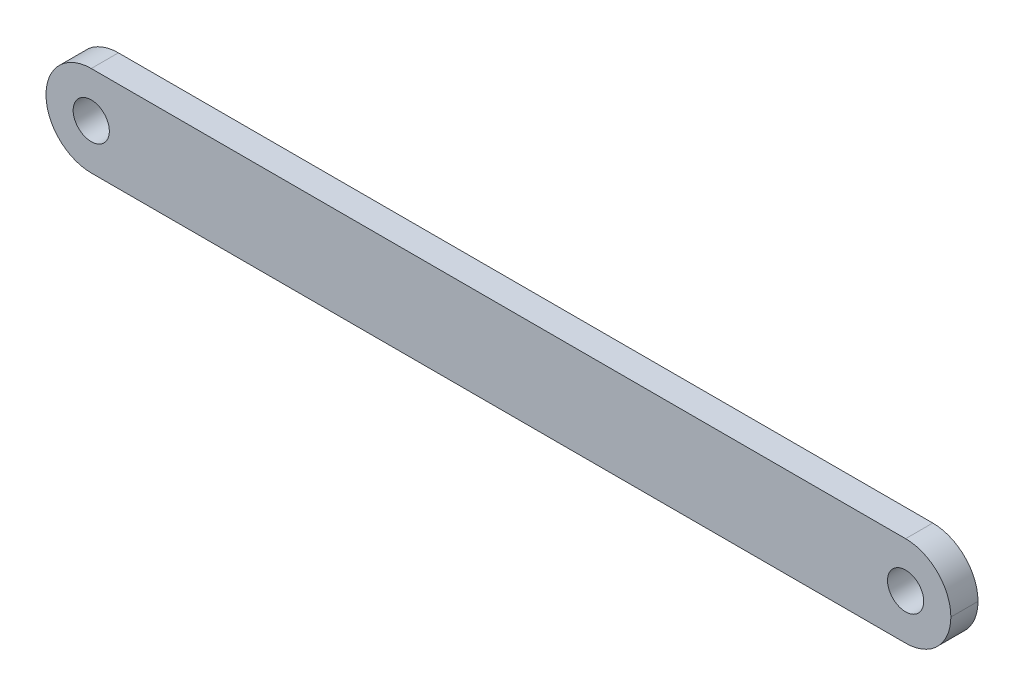
SolidWorks part; units mm, degrees
ref_plane "前视基准面" through (0, 0, 0) normal (0, 0, 1) x (1, 0, 0)
ref_plane "上视基准面" through (0, 0, 0) normal (0, 1, 0) x (1, 0, 0)
ref_plane "右视基准面" through (0, 0, 0) normal (1, 0, 0) x (0, 0, -1)
other "Configuration Table"
sketch "草图1" plane through (0, 0, 0) normal (0, 0, 1) x (1, 0, 0)
  line L0 (-50, 0) -> (-45, 0) construction
  line L1 (-50, -5) -> (50, -5)
  line L2 (-50, -5) -> (-50, 5)
  line L3 (-50, 5) -> (50, 5)
  line L4 (50, -5) -> (50, 5)
  line L5 (-50, -5) -> (50, 5) construction
  line L6 (-50, 5) -> (50, -5) construction
  line L7 (50, 0) -> (45, 0) construction
  circle A0 centre (-45, 0) radius 2
  circle A1 centre (45, 0) radius 2
  point P0 (0, 0)
  dimension "D1" = 10
  dimension "D2" = 100
extrude "凸台-拉伸1" add sketch "草图1" along normal blind 3
fillet "圆角1" radius 5 4 edges at (50, -5, 1.5) (50, 5, 1.5) (-50, -5, 1.5) (-50, 5, 1.5)
